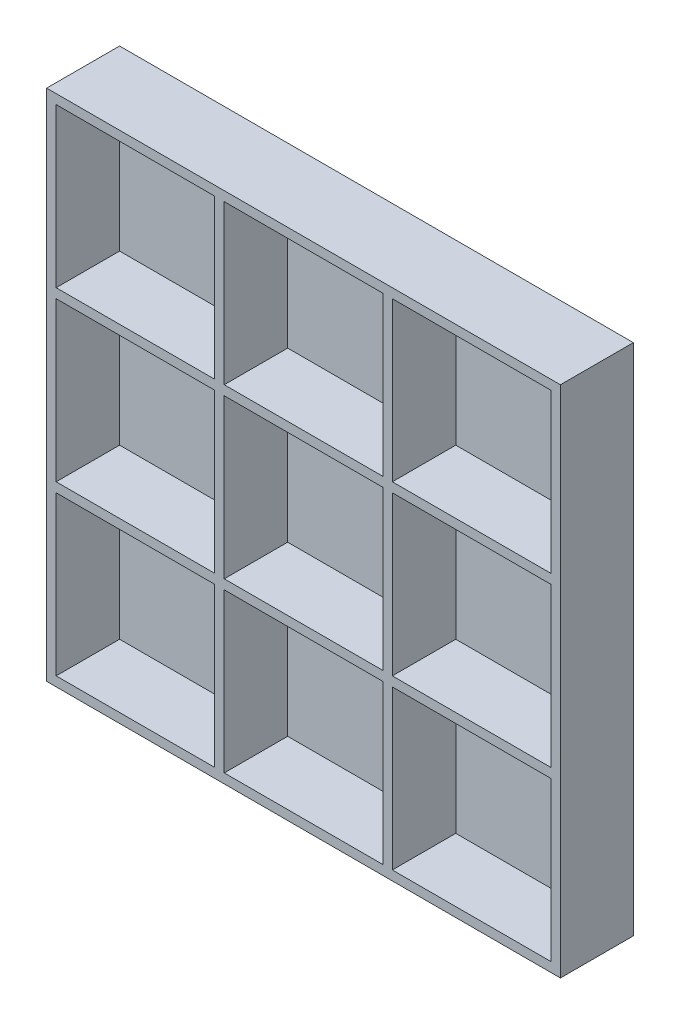
SolidWorks part; units mm, degrees
ref_plane "Front Plane" through (0, 0, 0) normal (0, 0, 1) x (1, 0, 0)
ref_plane "Top Plane" through (0, 0, 0) normal (0, 1, 0) x (1, 0, 0)
ref_plane "Right Plane" through (0, 0, 0) normal (1, 0, 0) x (0, 0, -1)
sketch "Sketch1" plane through (0, 0, 0) normal (0, 0, 1) x (1, 0, 0)
  line L1 (83.2209, 52.407) -> (-78.7791, 52.407)
  line L2 (83.2209, 52.407) -> (83.2209, -109.593)
  line L3 (83.2209, -109.593) -> (-78.7791, -109.593)
  line L4 (-78.7791, 52.407) -> (-78.7791, -109.593)
  line L5 (-75.7791, 49.407) -> (-25.7791, 49.407)
  line L6 (-75.7791, 49.407) -> (-75.7791, -0.593)
  line L7 (-75.7791, -0.593) -> (-25.7791, -0.593)
  line L8 (-25.7791, 49.407) -> (-25.7791, -0.593)
  line L9 (-22.7791, 49.407) -> (27.2209, 49.407)
  line L10 (-22.7791, 49.407) -> (-22.7791, -0.593)
  line L11 (-22.7791, -0.593) -> (27.2209, -0.593)
  line L12 (27.2209, 49.407) -> (27.2209, -0.593)
  line L13 (30.2209, 49.407) -> (80.2209, 49.407)
  line L14 (30.2209, 49.407) -> (30.2209, -0.593)
  line L15 (30.2209, -0.593) -> (80.2209, -0.593)
  line L16 (80.2209, 49.407) -> (80.2209, -0.593)
  line L17 (-75.7791, -3.593) -> (-25.7791, -3.593)
  line L18 (-75.7791, -3.593) -> (-75.7791, -53.593)
  line L19 (-75.7791, -53.593) -> (-25.7791, -53.593)
  line L20 (-25.7791, -3.593) -> (-25.7791, -53.593)
  line L21 (-22.7791, -3.593) -> (27.2209, -3.593)
  line L22 (-22.7791, -3.593) -> (-22.7791, -53.593)
  line L23 (-22.7791, -53.593) -> (27.2209, -53.593)
  line L24 (27.2209, -3.593) -> (27.2209, -53.593)
  line L25 (30.2209, -3.593) -> (80.2209, -3.593)
  line L26 (30.2209, -3.593) -> (30.2209, -53.593)
  line L27 (30.2209, -53.593) -> (80.2209, -53.593)
  line L28 (80.2209, -3.593) -> (80.2209, -53.593)
  line L29 (-75.7791, -56.593) -> (-25.7791, -56.593)
  line L30 (-75.7791, -56.593) -> (-75.7791, -106.593)
  line L31 (-75.7791, -106.593) -> (-25.7791, -106.593)
  line L32 (-25.7791, -56.593) -> (-25.7791, -106.593)
  line L33 (-22.7791, -56.593) -> (27.2209, -56.593)
  line L34 (-22.7791, -56.593) -> (-22.7791, -106.593)
  line L35 (-22.7791, -106.593) -> (27.2209, -106.593)
  line L36 (27.2209, -56.593) -> (27.2209, -106.593)
  line L37 (30.2209, -56.593) -> (80.2209, -56.593)
  line L38 (30.2209, -56.593) -> (30.2209, -106.593)
  line L39 (30.2209, -106.593) -> (80.2209, -106.593)
  line L40 (80.2209, -56.593) -> (80.2209, -106.593)
  point P41 (0, 0)
  dimension "D1" = 162
  dimension "D2" = 162
  dimension "D3" = 3
  dimension "D4" = 3
  dimension "D5" = 3
  dimension "D6" = 3
  dimension "D7" = 50
  dimension "D8" = 3
  dimension "D9" = 3
extrude "Boss-Extrude1" add sketch "Sketch1" along normal blind 23
extrude "Boss-Extrude2" add sketch "Sketch1<2>" along normal blind 3 contours L8 L5 L6 L7 | L12 L9 L10 L11 | L16 L13 L14 L15 | L28 L25 L26 L27 | L24 L21 L22 L23 | L20 L17 L18 L19 | L32 L29 L30 L31 | L36 L33 L34 L35 | L40 L37 L38 L39 | L1 L4 L3 L2 L5 L8 L7 L6 L9 L12 L11 L10 L13 L16 L15 L14 L17 L20 L19 L18 L21 L24 L23 L22 L25 L28 L27 L26 L29 L32 L31 L30 L33 L36 L35 L34 L37 L40 L39 L38 region at (80.9299, -28.593, 0) region at (-50.7791, 24.407, 0) region at (2.2209, 24.407, 0) region at (55.2209, 24.407, 0) region at (-50.7791, -28.593, 0) region at (2.2209, -28.593, 0) region at (55.2209, -28.593, 0) region at (-50.7791, -81.593, 0) region at (2.2209, -81.593, 0) region at (55.2209, -81.593, 0)
sketch "Sketch1<2>" plane through (0, 0, 0) normal (0, 0, 1) x (1, 0, 0) same geometry as "Sketch1"
